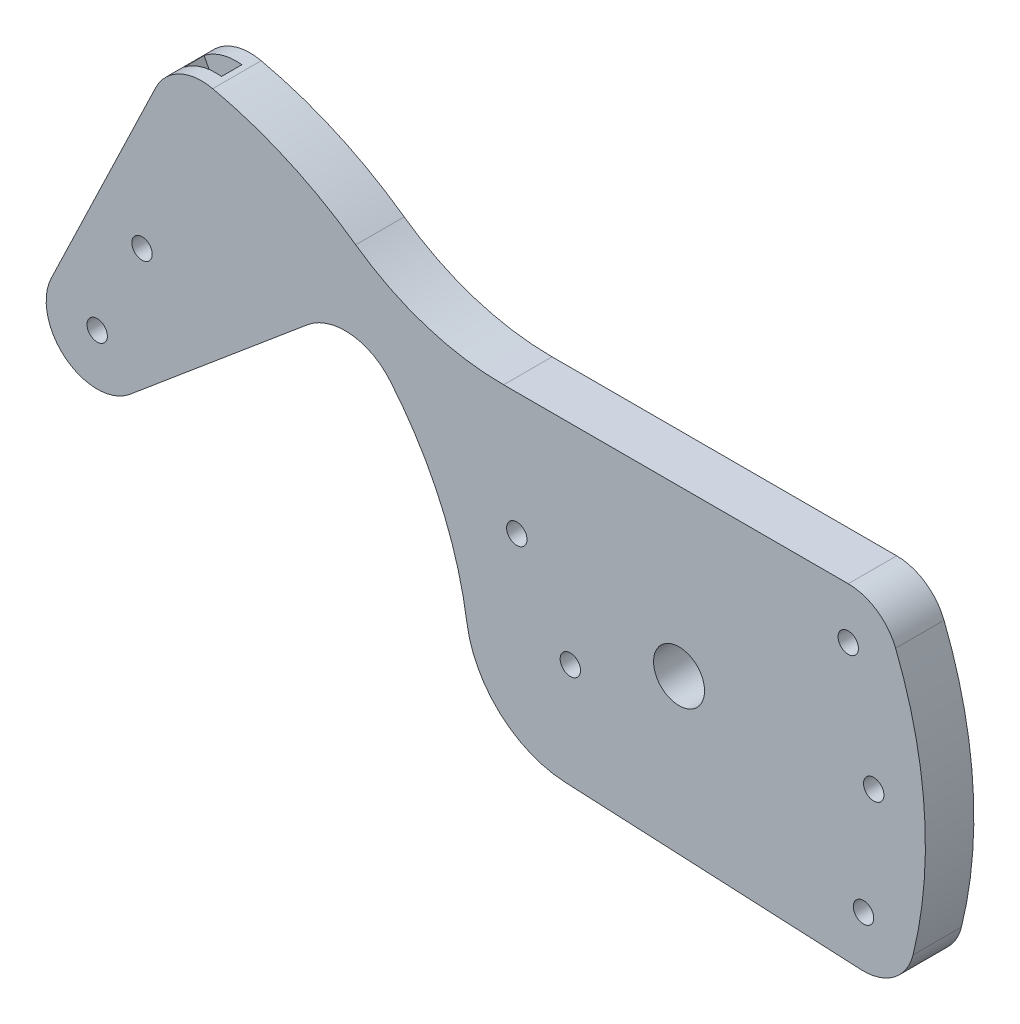
SolidWorks part; units mm, degrees
ref_plane "Front Plane" through (0, 0, 0) normal (0, 0, 1) x (1, 0, 0)
ref_plane "Top Plane" through (0, 0, 0) normal (0, 1, 0) x (1, 0, 0)
ref_plane "Right Plane" through (0, 0, 0) normal (1, 0, 0) x (0, 0, -1)
sketch "Sketch1" plane through (0, 0, 0) normal (0, 0, 1) x (1, 0, 0)
  line L1 (-5, -5) -> (5, -5) construction
  line L2 (-5, -5) -> (-5, 5) construction
  line L3 (-5, 5) -> (5, 5) construction
  line L4 (5, -5) -> (5, 5) construction
  line L5 (-5, -5) -> (5, 5) construction
  line L6 (-5, 5) -> (5, -5) construction
  line L7 (35.6989, -31.9883) -> (-22.3088, -29.1817)
  line L9 (-114.3299, 24.3337) -> (-123.1299, 6.0337)
  line L10 (-107.6899, -5.9604) -> (-72.8648, 23.2613)
  line L11 (-114.3299, 24.3337) -> (-102.6393, 48.6449)
  line L16 (-65.4725, 14.4515) -> (-108.3178, -21.5) construction
  line L17 (50.9822, -33.5) -> (-177.2181, -33.5) construction
  line L20 (-34.3975, 32.3) -> (33.1822, 32.3)
  circle A0 centre (0, 0) radius 5
  circle A1 centre (-31.8178, 8.3) radius 2
  circle A2 centre (-21.3178, -8.7) radius 2
  circle A3 centre (33.1822, 22.3) radius 2
  circle A4 centre (38.1822, -0.1) radius 2
  circle A5 centre (36.1822, -22) radius 2
  circle A6 centre (36.1822, -22) radius 2 construction
  circle A7 centre (38.1822, -0.1) radius 2 construction
  circle A8 centre (33.1822, 22.3) radius 2 construction
  circle A9 centre (-31.8178, 8.3) radius 2 construction
  circle A10 centre (-21.3178, -8.7) radius 2 construction
  arc A12 (-41.605, -11.6848) -> (-22.3088, -29.1817) centre (-21.3178, -8.7) ccw
  arc A13 (32.976, -31.8566) -> (28.2895, 32.3) centre (-34.3029, -4.5217) ccw construction
  arc A14 (45.8883, -24.4068) -> (42.4751, 25.9934) centre (-34.3029, -4.5217) ccw
  arc A15 (35.6989, -31.9883) -> (45.8883, -24.4068) centre (36.1822, -22) ccw
  arc A16 (42.4751, 25.9934) -> (33.1822, 32.3) centre (33.1822, 22.3) ccw
  circle A17 centre (-105.3178, 20) radius 2
  circle A18 centre (-34.3029, -4.5217) radius 82.6199 construction
  circle A19 centre (-114.1178, 1.7) radius 2
  circle A21 centre (-105.3178, 20) radius 2 construction
  circle A22 centre (-114.1178, 1.7) radius 2 construction
  circle A23 centre (-105.3178, 20) radius 10 construction
  arc A24 (-123.1299, 6.0337) -> (-107.6899, -5.9604) centre (-114.1178, 1.7) ccw
  arc A27 (-91.4485, 54.071) -> (-102.6393, 48.6449) centre (-93.6271, 44.3112) ccw
  circle A31 centre (-34.3029, -4.5217) radius 72.6199 construction
  arc A32 (-41.605, -11.6848) -> (-56.6627, 21.8438) centre (-108.3178, -21.5) ccw
  arc A33 (-31.0644, -26.7412) -> (-91.4485, 54.071) centre (-108.3178, -21.5) ccw
  arc A34 (-63.4016, 41.5721) -> (-34.3975, 32.3) centre (-34.3975, 82.3) ccw
  arc A35 (-56.6627, 21.8438) -> (-72.8648, 23.2613) centre (-65.4725, 14.4515) ccw
  circle A36 centre (-65.4725, 14.4515) radius 10.5004 construction
  circle A37 centre (-108.3178, -21.5) radius 67.4309 construction
  circle A38 centre (-108.3178, -21.5) radius 77.4309 construction
  circle A39 centre (-108.3178, -21.5) radius 10.5004 construction
  circle A40 centre (-108.3178, -21.5) radius 11.5004 construction
  circle A41 centre (0, 0) radius 33 construction
  point P35 (50.3427, -4.5217)
  point P37 (37.1696, 16.7103)
  point P54 (-36.0565, -0.0269)
  point P75 (-40.8381, -1.4887)
  dimension "D1" = 10
  dimension "D3" = 10
  dimension "D5" = 50
  dimension "D7" = 40
  dimension "D4" = 10
  dimension "D2" = 10
  dimension "D8" = 1
extrude "Boss-Extrude1" add sketch "Sketch1" along normal mid plane 9.5 contours A0 L4 L3 | A0 L1 L4 | A0 L2 L1 | A0 L3 L2 | A35 A32 A12 A33 A27 L11 L9 A24 L10 A17 A19 region at (6.7597, -29.2489, 0) region at (-82.5332, 21.292, 0)
sketch "Sketch2" plane through (0, 0, 0) normal (0, 0, 1) x (1, 0, 0)
  line L0 (-93.6271, 44.3112) -> (-96.4023, 53.9184) construction
  line L1 (-78.2271, 18.7618) -> (-72.8648, 23.2613)
  line L2 (-93.6271, 44.3112) -> (-84.6823, 13.3452) construction
  line L3 (-91.6689, 44.8769) -> (-78.2271, 18.7618)
  line L4 (-94.4967, 54.2733) -> (-93.6271, 44.3112) construction
  line L5 (-93.6271, 44.3112) -> (-90.4984, 8.4649) construction
  line L6 (-98.2036, 53.2026) -> (-93.6271, 44.3112) construction
  line L7 (-93.6271, 44.3112) -> (-79.798, 17.4436) construction
  line L8 (-99.8894, 52.1076) -> (-95.5854, 43.7456)
  line L9 (-92.4867, 54.246) -> (-91.6689, 44.8769)
  line L12 (-92.369, 6.8953) -> (-78.2271, 18.7618)
  line L13 (-107.6899, -5.9604) -> (-72.8648, 23.2613) construction
  line L14 (-100.8204, 53.9163) -> (-90.7503, 34.3517) construction
  line L15 (-92.6635, 56.2725) -> (-90.7503, 34.3517) construction
  line L16 (-95.5854, 43.7456) -> (-92.369, 6.8953)
  line L18 (-96.504, 54.2707) -> (-78.2271, 18.7618) construction
  line L19 (-96.504, 54.2707) -> (-92.369, 6.8953) construction
  line L20 (-92.369, 6.8953) -> (-107.6899, -5.9604)
  line L22 (-93.6271, 44.3112) -> (-90.3766, 7.0692) construction
  line L23 (-93.6271, 44.3112) -> (-80.0054, 17.8465) construction
  arc A0 (-92.4867, 54.246) -> (-99.8894, 52.1076) centre (-93.6271, 44.3112) ccw
  arc A1 (-94.4967, 54.2733) -> (-98.2036, 53.2026) centre (-93.6271, 44.3112) ccw construction
  arc A2 (-92.6635, 56.2725) -> (-100.8204, 53.9163) centre (-93.6271, 44.3112) ccw construction
  arc A3 (-91.4485, 54.071) -> (-102.6393, 48.6449) centre (-93.6271, 44.3112) ccw construction
  point P33 (-96.4023, 53.9184)
  dimension "D3" = 7
  dimension "D4" = 20
  dimension "D1" = 2
  dimension "D2" = 2
extrude "Cut-Extrude1" cut sketch "Sketch2" against normal mid plane 4 contours A0 L8 L12 L9 region at (-89.6335, 28.8858, 0)
